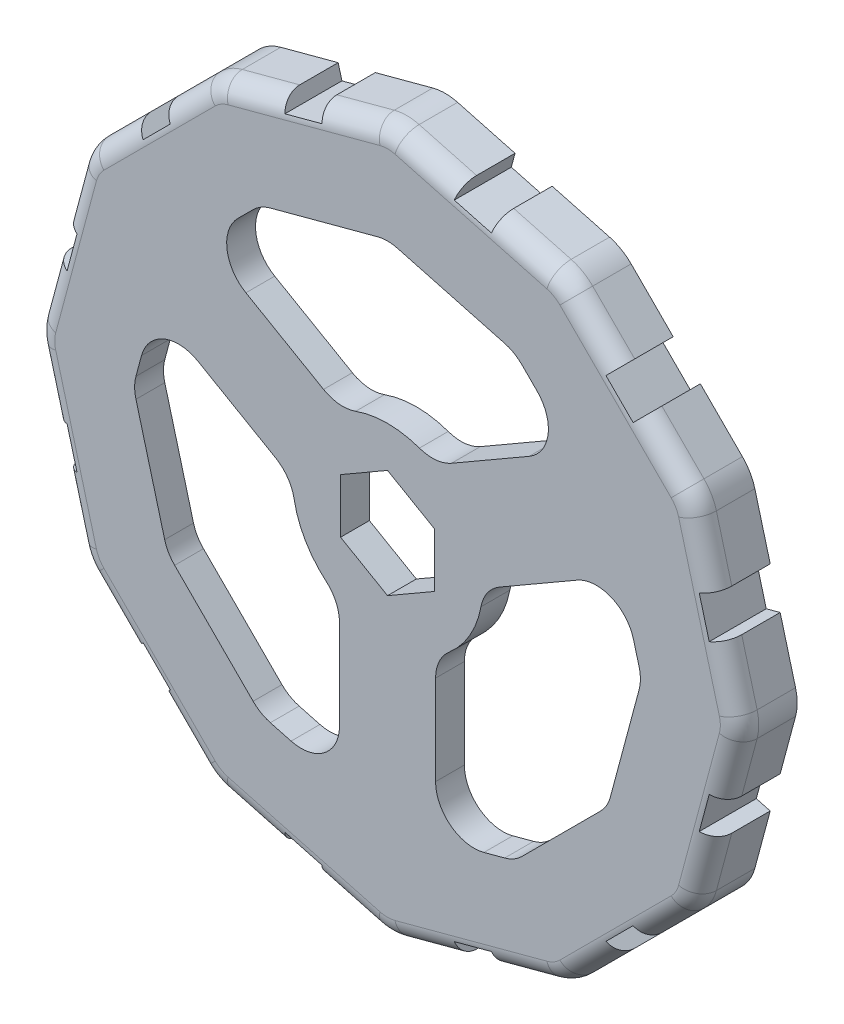
SolidWorks part; units mm, degrees
ref_plane "Front Plane" through (0, 0, 0) normal (0, 0, 1) x (1, 0, 0)
ref_plane "Top Plane" through (0, 0, 0) normal (0, 1, 0) x (1, 0, 0)
ref_plane "Right Plane" through (0, 0, 0) normal (1, 0, 0) x (0, 0, -1)
sketch "Sketch1" plane through (0, 0, 0) normal (0, 0, 1) x (1, 0, 0)
  line L0 (0, -36.8144) -> (18.4072, -31.8822)
  line L1 (0, 5.6436) -> (-4.8875, 2.8218)
  line L2 (-4.8875, 2.8218) -> (-4.8875, -2.8218)
  line L3 (-4.8875, -2.8218) -> (0, -5.6436)
  line L4 (0, -5.6436) -> (4.8875, -2.8218)
  line L5 (4.8875, -2.8218) -> (4.8875, 2.8218)
  line L6 (4.8875, 2.8218) -> (0, 5.6436)
  line L7 (0, 36.8144) -> (-18.4072, 31.8822)
  line L8 (-18.4072, 31.8822) -> (-31.8822, 18.4072)
  line L9 (-31.8822, 18.4072) -> (-36.8144, 0)
  line L10 (-36.8144, 0) -> (-31.8822, -18.4072)
  line L11 (-31.8822, -18.4072) -> (-18.4072, -31.8822)
  line L12 (-18.4072, -31.8822) -> (0, -36.8144)
  line L13 (18.4072, -31.8822) -> (31.8822, -18.4072)
  line L14 (31.8822, -18.4072) -> (36.8144, 0)
  line L15 (36.8144, 0) -> (31.8822, 18.4072)
  line L16 (31.8822, 18.4072) -> (18.4072, 31.8822)
  line L17 (18.4072, 31.8822) -> (0, 36.8144)
  line L18 (0, -31.638) -> (15.819, -27.3993)
  line L19 (15.819, -27.3993) -> (27.3993, -15.819)
  line L20 (27.3993, -15.819) -> (31.638, 0)
  line L21 (31.638, 0) -> (27.3993, 15.819)
  line L22 (27.3993, 15.819) -> (15.819, 27.3993)
  line L23 (15.819, 27.3993) -> (0, 31.638)
  line L24 (0, 31.638) -> (-15.819, 27.3993)
  line L25 (-15.819, 27.3993) -> (-27.3993, 15.819)
  line L26 (-27.3993, 15.819) -> (-31.638, 0)
  line L27 (-31.638, 0) -> (-27.3993, -15.819)
  line L28 (-27.3993, -15.819) -> (-15.819, -27.3993)
  line L29 (-15.819, -27.3993) -> (0, -31.638)
  circle A0 centre (0, 0) radius 4.8875 construction
  circle A1 centre (0, 0) radius 35.56 construction
  dimension "D1" = 5
extrude "Boss-Extrude1" add sketch "Sketch1" along normal blind 3 contours L28 L29 L18 L19 L20 L21 L22 L23 L24 L25 L26 L27 L6 L5 L4 L3 L2 L1 | L16 L17 L7 L8 L9 L10 L11 L12 L0 L13 L14 L15 L29 L28 L27 L26 L25 L24 L23 L22 L21 L20 L19 L18 region at (-8.9341, -33.3425, 0) region at (-7.6779, -28.6543, 0)
extrude "Boss-Extrude2" add sketch "Sketch1<3>" against normal blind 3 contours L16 L17 L7 L8 L9 L10 L11 L12 L0 L13 L14 L15 L29 L28 L27 L26 L25 L24 L23 L22 L21 L20 L19 L18 region at (-8.9341, -33.3425, 0)
sketch "Sketch1<3>" plane through (0, 0, 0) normal (0, 0, 1) x (1, 0, 0) same geometry as "Sketch1"
sketch "Sketch2" plane through (0, 0, 3) normal (0, 0, 1) x (1, 0, 0)
  line L0 (0, 0) -> (9.2036, 34.3483)
  line L2 (7.2718, 34.866) -> (11.1355, 33.8307)
  line L3 (11.1355, 33.8307) -> (10.7472, 32.3818)
  line L4 (10.7472, 32.3818) -> (6.8835, 33.4171)
  line L5 (6.8835, 33.4171) -> (7.2718, 34.866)
  point P8 (9.2036, 34.3483)
  dimension "D1" = 1.5
  dimension "D2" = 0
  dimension "D3" = 35.56
extrude "Cut-Extrude1" cut sketch "Sketch2" against normal through all contours L5 L2 L3 L4
fillet "Fillet1" radius 5 12 edges at (-18.4072, 31.8822, 0) (-31.8822, 18.4072, 0) (-36.8144, 0, 0) (-31.8822, -18.4072, 0) (-18.4072, -31.8822, 0) (0, -36.8144, 0) (18.4072, -31.8822, 0) (31.8822, -18.4072, 0) (36.8144, 0, 0) (31.8822, 18.4072, 0) (18.4072, 31.8822, 0) (0, 36.8144, 0)
sketch "Sketch4" plane through (0, 0, 0) normal (0, 0, -1) x (-1, 0, 0)
  line L0 (-4.8875, 2.8218) -> (-27.3993, 15.819)
  line L1 (4.8875, 2.8218) -> (27.3993, 15.819)
  line L3 (13.2308, 22.9165) -> (0, 26.4617)
  line L4 (0, 26.4617) -> (-13.2308, 22.9165)
  line L5 (-13.2308, 22.9165) -> (-19.2562, 16.8911)
  line L6 (-4.8875, 8.5953) -> (-19.2562, 16.8911)
  line L7 (4.8875, 8.5953) -> (19.2562, 16.8911)
  line L8 (19.2562, 16.8911) -> (13.2308, 22.9165)
  line L9 (23.8638, 12.2835) -> (13.2308, 22.9165) construction
  line L10 (23.7391, 19.4793) -> (24.8993, 20.1491)
  line L12 (-2.3875, 7.1519) -> (-24.8993, 20.1491) construction
  line L14 (0, -31.638) -> (15.819, -27.3993)
  line L15 (15.819, -27.3993) -> (27.3993, -15.819)
  line L16 (27.3993, -15.819) -> (31.638, 0)
  line L17 (31.638, 0) -> (27.3993, 15.819)
  line L18 (27.3993, 15.819) -> (15.819, 27.3993)
  line L19 (15.819, 27.3993) -> (0, 31.638)
  line L20 (0, 31.638) -> (-15.819, 27.3993)
  line L21 (-15.819, 27.3993) -> (-27.3993, 15.819)
  line L22 (-27.3993, 15.819) -> (-31.638, 0)
  line L23 (-31.638, 0) -> (-27.3993, -15.819)
  line L24 (-27.3993, -15.819) -> (-15.819, -27.3993)
  line L25 (-15.819, -27.3993) -> (0, -31.638)
  line L26 (0, -31.638) -> (15.819, -27.3993)
  line L27 (15.819, -27.3993) -> (27.3993, -15.819)
  line L28 (27.3993, -15.819) -> (31.638, 0)
  line L29 (31.638, 0) -> (27.3993, 15.819)
  line L30 (27.3993, 15.819) -> (15.819, 27.3993)
  line L31 (15.819, 27.3993) -> (0, 31.638)
  line L32 (0, 31.638) -> (-15.819, 27.3993)
  line L33 (-15.819, 27.3993) -> (-27.3993, 15.819)
  line L34 (-27.3993, 15.819) -> (-31.638, 0)
  line L35 (-31.638, 0) -> (-27.3993, -15.819)
  line L36 (-27.3993, -15.819) -> (-15.819, -27.3993)
  line L37 (-15.819, -27.3993) -> (0, -31.638)
  line L41 (5, -8.5304) -> (5, -25.1219)
  line L42 (-13.2308, 22.9165) -> (-23.8638, 12.2835) construction
  line L43 (2.3875, 7.1519) -> (24.8993, 20.1491) construction
  line L44 (5, -25.1219) -> (13.2308, -22.9165)
  line L45 (13.2308, -22.9165) -> (22.9165, -13.2308)
  line L46 (22.9165, -13.2308) -> (26.4617, 0)
  line L47 (26.4617, 0) -> (24.2562, 8.2308)
  line L48 (9.8875, -0.065) -> (24.2562, 8.2308)
  line L51 (-9.8875, -0.065) -> (-24.2562, 8.2308)
  line L52 (-24.2562, 8.2308) -> (-26.4617, 0)
  line L53 (-26.4617, 0) -> (-22.9165, -13.2308)
  line L54 (-22.9165, -13.2308) -> (-13.2308, -22.9165)
  line L55 (-13.2308, -22.9165) -> (-5, -25.1219)
  line L56 (-5, -8.5304) -> (-5, -25.1219)
  arc A0 (4.8875, 8.5953) -> (-4.8875, 8.5953) centre (0, 0) ccw
  arc A1 (-9.8875, -0.065) -> (-5, -8.5304) centre (0, 0) ccw
  arc A2 (5, -8.5304) -> (9.8875, -0.065) centre (0, 0) ccw
  point P54 (0, 0)
  dimension "D1" = 0
  dimension "D6" = 3
  dimension "D2" = 5
  dimension "D3" = 5
  dimension "D4" = 5
extrude "Cut-Extrude2" cut sketch "Sketch4" against normal blind 3 contours L56 L51 L52 L53 L54 L55 | L6 L7 L8 L3 L4 L5 | L48 L41 L44 L45 L46 L47 region at (0, 17.5627, 0) region at (-15.2097, -8.7813, 0) region at (15.2097, -8.7813, 0)
fillet "Fillet3" radius 4 21 edges at (24.2562, 8.2308, 1.5) (5, -25.1219, 1.5) (19.2562, 16.8911, 1.5) (-19.2562, 16.8911, 1.5) (-4.8875, 8.5953, 1.5) (4.8875, 8.5953, 1.5) (9.8875, -0.065, 1.5) (5, -8.5304, 1.5) (-5, -8.5304, 1.5) (-9.8875, -0.065, 1.5) (-5, -25.1219, 1.5) (-24.2562, 8.2308, 1.5) (13.2308, 22.9165, 1.5) (0, 26.4617, 1.5) (-13.2308, 22.9165, 1.5) (26.4617, 0, 1.5) (22.9165, -13.2308, 1.5) (13.2308, -22.9165, 1.5) (-13.2308, -22.9165, 1.5) (-22.9165, -13.2308, 1.5) (-26.4617, 0, 1.5)
fillet "Fillet4" radius 2 25 edges at (9.2036, -34.3483, 3) (0, -36.638, 3) (-9.2036, -34.3483, 3) (4.2829, 35.6668, 3) (0, 36.638, 3) (-9.2036, 34.3483, 3) (-18.319, 31.7295, 3) (-25.1447, 25.1447, 3) (-31.7295, 18.319, 3) (-34.3483, 9.2036, 3) (-36.638, 0, 3) (-34.3483, -9.2036, 3) (-31.7295, -18.319, 3) (-25.1447, -25.1447, 3) (-18.319, -31.7295, 3) (14.1243, 33.0298, 3) (18.319, 31.7295, 3) (25.1447, 25.1447, 3) (31.7295, 18.319, 3) (34.3483, 9.2036, 3) (36.638, 0, 3) (34.3483, -9.2036, 3) (31.7295, -18.319, 3) (25.1447, -25.1447, 3) (18.319, -31.7295, 3)
pattern_circular "CirPattern1" count 12 over 360 about axis through (0, 0, 3) along (0, 0, -1) of "Cut-Extrude1"
fillet "Fillet5" radius 3 12 edges at (27.3993, 15.819, -1.5) (31.638, 0, -1.5) (27.3993, -15.819, -1.5) (15.819, -27.3993, -1.5) (15.819, 27.3993, -1.5) (0, 31.638, -1.5) (-15.819, 27.3993, -1.5) (-27.3993, 15.819, -1.5) (-31.638, 0, -1.5) (-27.3993, -15.819, -1.5) (-15.819, -27.3993, -1.5) (0, -31.638, -1.5)
